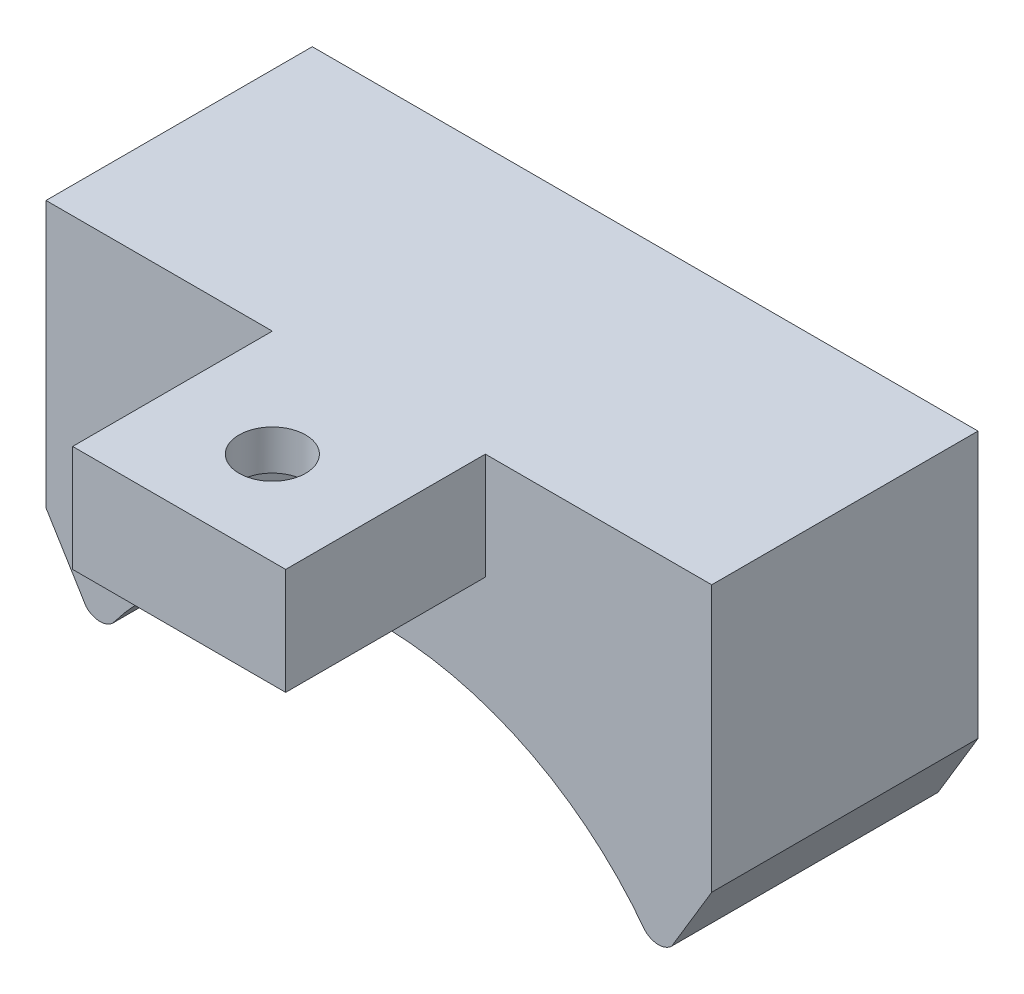
SolidWorks part; units mm, degrees
ref_plane "Front Plane" through (0, 0, 0) normal (0, 0, 1) x (1, 0, 0)
ref_plane "Top Plane" through (0, 0, 0) normal (0, 1, 0) x (1, 0, 0)
ref_plane "Right Plane" through (0, 0, 0) normal (1, 0, 0) x (0, 0, -1)
sketch "Sketch1" plane through (0, 0, 0) normal (0, 0, 1) x (1, 0, 0)
  line L0 (0, -5) -> (0, -5.0033)
  line L1 (-25, 10) -> (25, 10)
  line L2 (-25, 10) -> (-25, -10)
  line L3 (-25, -10) -> (-14.9972, -10)
  line L4 (25, 10) -> (25, -10)
  line L5 (-25, 10) -> (25, -10) construction
  line L6 (-25, -10) -> (25, 10) construction
  line L7 (-25, -10) -> (-21.995, -14.9)
  line L8 (22, -15) -> (25, -10)
  line L9 (14.9972, -10) -> (25, -10)
  arc A2 (-20, -15) -> (20, -15) centre (0, -30.0083) cw
  arc A5 (-21.995, -14.9) -> (-20, -15) centre (-20.9475, -13.9525) ccw
  arc A6 (20, -15) -> (22, -15) centre (21, -14) ccw
  point P0 (0, 0)
  point P9 (0, 0)
  point P10 (0, -5)
  dimension "D1" = 50
  dimension "D2" = 20
  dimension "D3" = 5
extrude "Boss-Extrude1" add sketch "Sketch1" along normal blind 20 contours L7 A5 A2 L3 | L3 A2 L9 L4 L1 L2 | A2 A6 L8 L9 region at (0, 0.9078, 0) region at (-20.4971, -11.9687, 0) region at (20.5137, -11.9874, 0)
sketch "Sketch2" plane through (0, 0, 20) normal (0, 0, 1) x (1, 0, 0)
  line L0 (0, 10) -> (-8, 10)
  line L1 (-25, 10) -> (25, 10) construction
  line L2 (-8, 10) -> (-8, 2)
  line L3 (-8, 2) -> (8, 2)
  line L4 (8, 2) -> (8, 10)
  line L5 (8, 10) -> (0, 10)
  dimension "D1" = 8
  dimension "D2" = 8
  dimension "D3" = 8
  dimension "D4" = 8
extrude "Boss-Extrude2" add sketch "Sketch2" along normal blind 15
sketch "Sketch4" plane through (0, 2, 0) normal (0, -1, 0) x (1, 0, 0)
  line L0 (-8, 35) -> (8, 35) construction
  line L2 (2.4573, 23.7559) -> (4.9007, 28.0119)
  line L3 (4.9007, 28.0119) -> (2.4367, 32.2559)
  line L4 (2.4367, 32.2559) -> (-2.4707, 32.2441)
  line L5 (-2.4707, 32.2441) -> (-4.9142, 27.9881)
  line L6 (-4.9142, 27.9881) -> (-2.4502, 23.7441)
  line L7 (-2.4502, 23.7441) -> (2.4573, 23.7559)
  circle A0 centre (-0.0067, 28) radius 4.25 construction
  point P0 (0, 35)
  point P1 (-0.0067, 28)
  dimension "D2" = 7
  dimension "D3" = 8.5
extrude "Cut-Extrude1" cut sketch "Sketch4" against normal blind 5
sketch "Sketch5" plane through (0, 7, 0) normal (0, -1, 0) x (1, 0, 0)
  line L0 (-2.4502, 23.7441) -> (2.4573, 23.7559) construction
  circle A0 centre (0, 28) radius 2.5
  point P4 (0.0036, 23.75)
  dimension "D1" = 4.25
  dimension "D2" = 2.4502
extrude "Cut-Extrude2" cut sketch "Sketch5" against normal up to surface (3 mm away) contours A0 up to face at (0, 10, 18.75)
